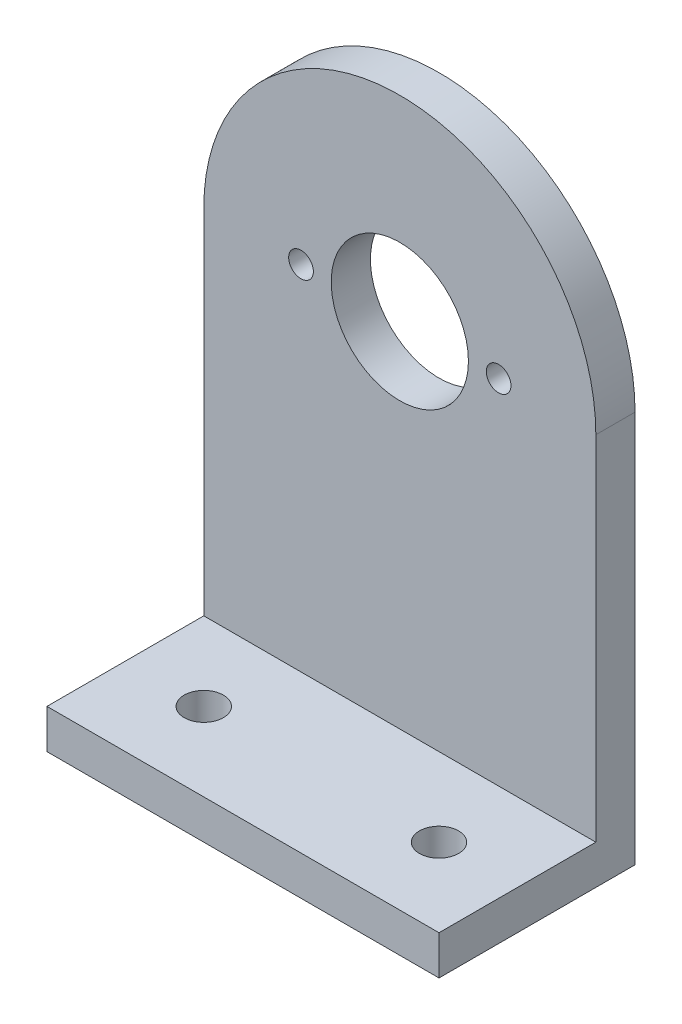
SolidWorks part; units mm, degrees
ref_plane "Front Plane" through (0, 0, 0) normal (0, 0, 1) x (1, 0, 0)
ref_plane "Top Plane" through (0, 0, 0) normal (0, 1, 0) x (1, 0, 0)
ref_plane "Right Plane" through (0, 0, 0) normal (1, 0, 0) x (0, 0, -1)
sketch "Sketch1" plane through (0, 0, 0) normal (0, 0, 1) x (1, 0, 0)
  line L1 (-15.875, 0) -> (15.875, 0)
  line L2 (-15.875, 0) -> (-15.875, -31.75)
  line L3 (-15.875, -31.75) -> (15.875, -31.75)
  line L4 (15.875, 0) -> (15.875, -31.75)
  circle A0 centre (0, 0) radius 15.875
  arc A2 (-15.875, 0) -> (15.875, 0) centre (0, 0) ccw
  dimension "D1" = 31.75
  dimension "D2" = 31.75
extrude "Boss-Extrude1" add sketch "Sketch1" along normal blind 3.175 contours A0 | L2 L1 L4 L3
sketch "Sketch3" plane through (0, 0, 3.175) normal (0, 0, 1) x (1, 0, 0)
  circle A0 centre (0, 0) radius 5.5562
  dimension "D1" = 11.1125
extrude "Cut-Extrude1" cut sketch "Sketch3" against normal through all
sketch "Sketch4" plane through (0, 0, 3.175) normal (0, 0, 1) x (1, 0, 0)
  line L0 (15.875, 0) -> (15.875, -31.75) construction
  line L1 (-15.875, -31.75) -> (15.875, -31.75)
  line L2 (-15.875, -31.75) -> (-15.875, -28.575)
  line L3 (-15.875, -28.575) -> (15.875, -28.575)
  line L4 (15.875, -31.75) -> (15.875, -28.575)
  dimension "D1" = 3.175
extrude "Boss-Extrude2" add sketch "Sketch4" along normal blind 12.7
sketch "Sketch5" plane through (0, -28.575, 0) normal (0, 1, 0) x (1, 0, 0)
  line L0 (-15.875, -9.525) -> (15.875, -9.525) construction
  line L1 (-15.875, -15.875) -> (-15.875, -3.175) construction
  line L2 (15.875, -15.875) -> (15.875, -3.175) construction
  line L3 (0, -3.175) -> (0, -15.875) construction
  line L4 (15.875, -3.175) -> (-15.875, -3.175) construction
  line L5 (15.875, -15.875) -> (-15.875, -15.875) construction
  circle A0 centre (-9.525, -9.525) radius 1.5875
  circle A1 centre (9.525, -9.525) radius 1.5875
  dimension "D1" = 3.175
  dimension "D2" = 9.525
extrude "Cut-Extrude2" cut sketch "Sketch5" against normal through all
hole_wizard "Ø2.0mm Dowel Hole1" positions "Sketch8" profile "Sketch9" hole size "Ø2.0" standard "ANSI Metric"
sketch "Sketch8" plane through (0, 0, 3.175) normal (0, 0, 1) x (1, 0, 0)
  line L0 (-15.875, 0) -> (15.875, 0) construction
  point P0 (-8.001, 0)
  point P2 (8.001, 0)
  dimension "D1" = 16.002
  dimension "D2" = 8.001
sketch "Sketch9" plane through (-8.001, 0, 3.175) normal (1, 0, 0) x (0, -1, 0)
  line L0 (0, 0) -> (0, 13.3009)
  line L1 (0, 13.3009) -> (1, 12.7)
  line L2 (1, 12.7) -> (1, 0)
  line L5 (1, 0) -> (0, 0)
  line L10 (0, 13.3009) -> (-1, 12.7) construction
  line L11 (0, -6.35) -> (0, 107.95) construction
  dimension "Hole Dia." = 2
  dimension "Hole Depth" = 12.7
  dimension "Drill Angle" = 118
